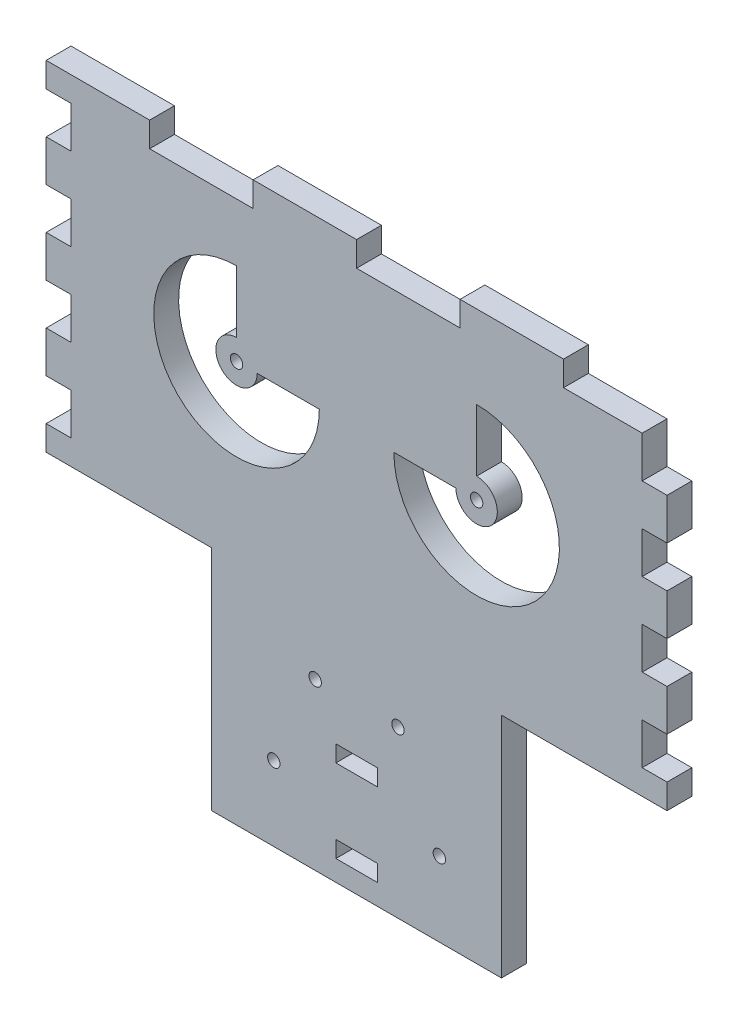
SolidWorks part; units mm, degrees
material "Pine"
ref_plane "Front Plane" through (0, 0, 0) normal (0, 0, 1) x (1, 0, 0)
ref_plane "Top Plane" through (0, 0, 0) normal (0, 1, 0) x (1, 0, 0)
ref_plane "Right Plane" through (0, 0, 0) normal (1, 0, 0) x (0, 0, -1)
sketch "Sketch1" plane through (0, 0, 0) normal (0, 0, 1) x (1, 0, 0)
  line L1 (75, -41) -> (-75, -41)
  line L2 (75, -41) -> (75, 41)
  line L3 (75, 41) -> (-75, 41)
  line L4 (-75, -41) -> (-75, 41)
  line L5 (75, -41) -> (-75, 41) construction
  line L6 (75, 41) -> (-75, -41) construction
  line L7 (-35, -41) -> (35, -41)
  line L8 (-35, -41) -> (-35, -96)
  line L9 (-35, -96) -> (35, -96)
  line L10 (35, -41) -> (35, -96)
  point P0 (0, 0)
  point P10 (0, -96)
  dimension "D1" = 150
  dimension "D2" = 82
  dimension "D3" = 55
  dimension "D4" = 70
  dimension "D5" = 0
extrude "Boss-Extrude1" add sketch "Sketch1" along normal blind 6 contours L10 L1 L8 L9 | L4 L1 L2 L3 region at (0, 0, 0) region at (0, -68.5, 0)
sketch "Sketch2" plane through (0, 0, 6) normal (0, 0, 1) x (1, 0, 0)
  line L0 (-75, -41) -> (-75, 41) construction
  line L1 (-75, 35) -> (-69, 35)
  line L2 (-75, 35) -> (-75, 25)
  line L3 (-75, 25) -> (-69, 25)
  line L4 (-69, 35) -> (-69, 25)
  line L5 (75, 41) -> (-75, 41) construction
  line L6 (69, 35) -> (69, 25)
  line L7 (69, 35) -> (75, 35)
  line L8 (75, 35) -> (75, 25)
  line L9 (69, 25) -> (75, 25)
  line L10 (69, 15) -> (69, 5)
  line L11 (69, 15) -> (75, 15)
  line L12 (75, 15) -> (75, 5)
  line L13 (69, 5) -> (75, 5)
  line L14 (-75, 15) -> (-75, 5)
  line L15 (-75, 15) -> (-69, 15)
  line L16 (-69, 15) -> (-69, 5)
  line L17 (-75, 5) -> (-69, 5)
  line L18 (-75, -5) -> (-75, -15)
  line L19 (-75, -5) -> (-69, -5)
  line L20 (-69, -5) -> (-69, -15)
  line L21 (-75, -15) -> (-69, -15)
  line L22 (69, -5) -> (69, -15)
  line L23 (69, -5) -> (75, -5)
  line L24 (75, -5) -> (75, -15)
  line L25 (69, -15) -> (75, -15)
  line L26 (-75, -25) -> (-75, -35)
  line L27 (-75, -25) -> (-69, -25)
  line L28 (-69, -25) -> (-69, -35)
  line L29 (-75, -35) -> (-69, -35)
  line L30 (69, -25) -> (69, -35)
  line L31 (69, -25) -> (75, -25)
  line L32 (75, -25) -> (75, -35)
  line L33 (69, -35) -> (75, -35)
  dimension "D1" = 6
  dimension "D2" = 10
  dimension "D3" = 6
  dimension "D4" = 2
  dimension "D5" = 4
extrude "Cut-Extrude1" cut sketch "Sketch2" against normal blind 10
sketch "Sketch3" plane through (0, 0, 6) normal (0, 0, 1) x (1, 0, 0)
  line L0 (-9, 1) -> (-24, 1)
  line L1 (-29, 21) -> (-29, 6)
  line L2 (-35, -41) -> (-75, -41) construction
  line L3 (9, 1) -> (24, 1)
  line L4 (29, 21) -> (29, 6)
  line L26 (0, -3.3) -> (0, 3.3) construction
  circle A0 centre (-29, 1) radius 1.5
  circle A4 centre (29, 1) radius 1.5
  arc A7 (-9, 1) -> (-29, 21) centre (-29, 1) cw
  arc A8 (-24, 1) -> (-29, 6) centre (-29, 1) cw
  arc A9 (9, 1) -> (29, 21) centre (29, 1) ccw
  arc A10 (24, 1) -> (29, 6) centre (29, 1) ccw
  dimension "D2" = 3
  dimension "D3" = 20
  dimension "D4" = 20
  dimension "D1" = 29
  dimension "D5" = 20
  dimension "D6" = 15
  dimension "D7" = 42
extrude "Cut-Extrude2" cut sketch "Sketch3" against normal blind 6
sketch "Sketch4" plane through (0, 0, 6) normal (0, 0, 1) x (1, 0, 0)
  line L0 (25, 41) -> (25, 35)
  line L1 (75, 41) -> (50, 41)
  line L2 (75, 41) -> (75, 35)
  line L3 (75, 35) -> (50, 35)
  line L4 (50, 41) -> (50, 35)
  line L5 (25, 41) -> (0, 41)
  line L6 (0, 41) -> (0, 35)
  line L7 (25, 35) -> (0, 35)
  line L8 (-25, 41) -> (-25, 35)
  line L9 (-25, 41) -> (-50, 41)
  line L10 (-50, 41) -> (-50, 35)
  line L11 (-25, 35) -> (-50, 35)
  dimension "D1" = 25
  dimension "D2" = 6
  dimension "D3" = 3
extrude "Cut-Extrude3" cut sketch "Sketch4" against normal blind 6
sketch "Sketch5" plane through (0, 0, 6) normal (0, 0, 1) x (1, 0, 0)
  line L0 (35, -41) -> (35, -96) construction
  line L1 (-5, -67) -> (5, -67)
  line L2 (-5, -67) -> (-5, -71)
  line L3 (-5, -71) -> (5, -71)
  line L4 (5, -67) -> (5, -71)
  line L5 (-5, -87) -> (5, -87)
  line L6 (-5, -87) -> (-5, -91)
  line L7 (-5, -91) -> (5, -91)
  line L8 (5, -87) -> (5, -91)
  line L9 (-35, -96) -> (35, -96) construction
  circle A0 centre (-10, -56) radius 1.5
  circle A1 centre (10, -56) radius 1.5
  circle A2 centre (-20, -78) radius 1.5
  circle A3 centre (20, -78) radius 1.5
  point P16 (5, -89)
  dimension "D2" = 3
  dimension "D4" = 3
  dimension "D14" = 18
  dimension "D16" = 40
  dimension "D19" = 15
  dimension "D20" = 25
  dimension "D5" = 10
  dimension "D6" = 4
  dimension "D7" = 10
  dimension "D8" = 4
  dimension "D9" = 30
  dimension "D10" = 30
  dimension "D11" = 5
  dimension "D12" = 25
extrude "Cut-Extrude4" cut sketch "Sketch5" against normal blind 10
